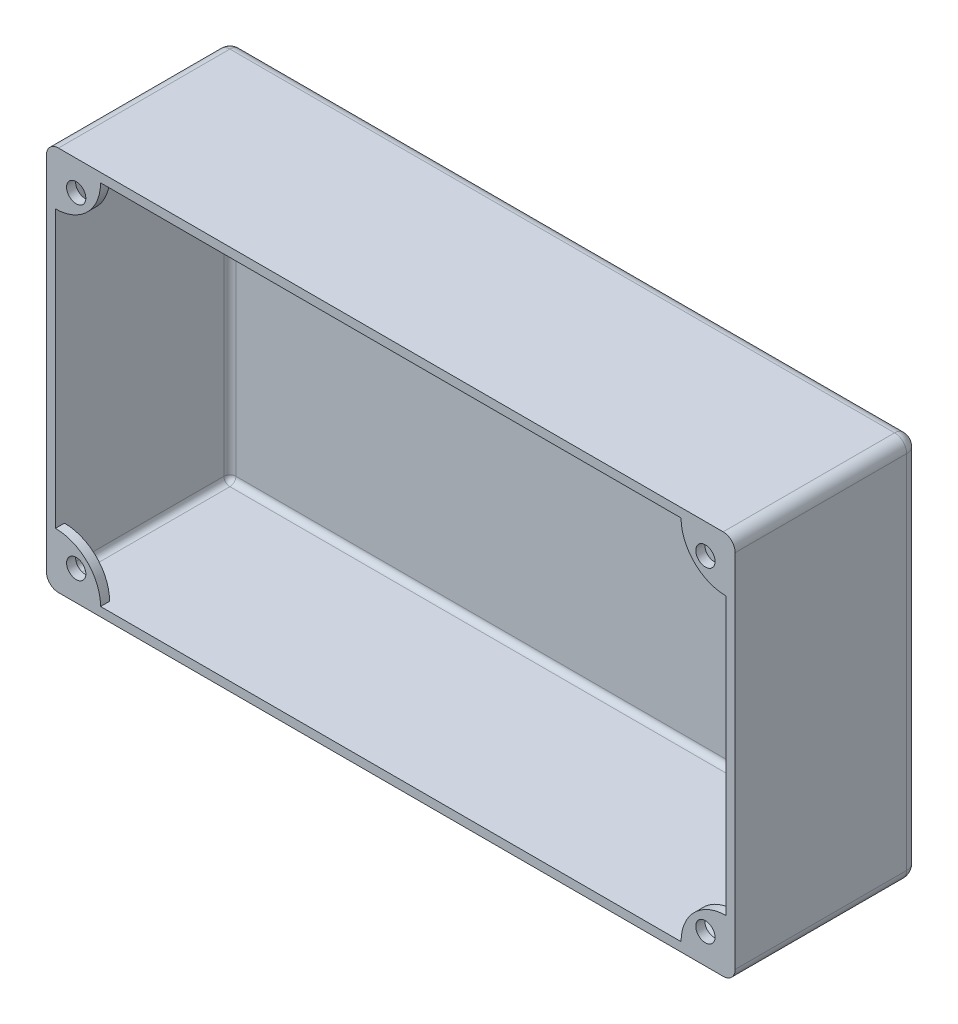
SolidWorks part; units mm, degrees
ref_plane "Plan de face" through (0, 0, 0) normal (0, 0, 1) x (1, 0, 0)
ref_plane "Plan de dessus" through (0, 0, 0) normal (0, 1, 0) x (1, 0, 0)
ref_plane "Plan de droite" through (0, 0, 0) normal (1, 0, 0) x (0, 0, -1)
sketch "Esquisse1" plane through (0, 0, 0) normal (0, 0, 1) x (1, 0, 0)
  line L1 (-78.4653, 42.1965) -> (36.0347, 42.1965)
  line L2 (-78.4653, 42.1965) -> (-78.4653, -21.8035)
  line L3 (-78.4653, -21.8035) -> (36.0347, -21.8035)
  line L4 (36.0347, 42.1965) -> (36.0347, -21.8035)
  line L5 (-78.4653, 42.1965) -> (36.0347, -21.8035) construction
  line L6 (-78.4653, -21.8035) -> (36.0347, 42.1965) construction
  point P0 (-21.2153, 10.1965)
  dimension "D1" = 114.5
  dimension "D2" = 64
extrude "Boss.-Extru.1" add sketch "Esquisse1" along normal blind 30.5
sketch "Esquisse2" plane through (0, 0, 30.5) normal (0, 0, 1) x (1, 0, 0)
  line L0 (-77.9182, 10.1965) -> (36.0347, 10.1965) construction
  line L1 (36.0347, -21.8035) -> (36.0347, 42.1965) construction
  line L2 (36.0347, 42.1965) -> (-78.4653, 42.1965) construction
  line L3 (-78.4653, 42.1965) -> (-78.4653, -21.8035) construction
  line L4 (-21.2153, 42.1965) -> (-21.2153, -21.8035) construction
  line L5 (-78.4653, -21.8035) -> (36.0347, -21.8035) construction
  line L14 (34.5347, -20.3035) -> (34.5347, 40.6965)
  line L15 (34.5347, 40.6965) -> (-76.9653, 40.6965)
  line L16 (-76.9653, 40.6965) -> (-76.9653, -20.3035)
  line L17 (-76.9653, -20.3035) -> (34.5347, -20.3035)
  line L18 (34.5347, -20.3035) -> (34.5347, 40.6965)
  line L19 (34.5347, 40.6965) -> (-76.9653, 40.6965)
  line L20 (-76.9653, 40.6965) -> (-76.9653, -20.3035)
  line L21 (-76.9653, -20.3035) -> (34.5347, -20.3035)
  circle A0 centre (-73.5153, 37.2465) radius 1.6
  circle A1 centre (31.0847, 37.2465) radius 1.6
  circle A2 centre (-73.5153, -16.8535) radius 1.6
  circle A3 centre (31.0847, -16.8535) radius 1.6
  arc A4 (-76.9653, 33.1965) -> (-69.4653, 40.6965) centre (-76.9653, 40.6965) ccw
  arc A5 (-76.9653, -12.8035) -> (-69.4653, -20.3035) centre (-76.9653, -20.3035) cw
  arc A6 (34.5347, -12.8035) -> (27.0347, -20.3035) centre (34.5347, -20.3035) ccw
  arc A7 (34.5347, 33.1965) -> (27.0347, 40.6965) centre (34.5347, 40.6965) cw
  dimension "D1" = 3.2
  dimension "D2" = 4.95
  dimension "D3" = 4.95
  dimension "D5" = 7.5
  dimension "D4" = 1.5
extrude "Enlèv. mat.-Extru.2" cut sketch "Esquisse2" against normal blind 1.5 contours L18 A7 L19 A4 L20 A5 L21 A6 region at (-21.2153, 10.1965, 30.5)
sketch "Esquisse3" plane through (0, 0, 29) normal (0, 0, 1) x (1, 0, 0)
  line L1 (-76.9653, -20.3035) -> (34.5347, -20.3035)
  line L2 (-76.9653, -20.3035) -> (-76.9653, 40.6965)
  line L3 (-76.9653, 40.6965) -> (34.5347, 40.6965)
  line L4 (34.5347, -20.3035) -> (34.5347, 40.6965)
  line L5 (27.0347, 40.6965) -> (-69.4653, 40.6965) construction
  line L6 (-69.4653, -20.3035) -> (27.0347, -20.3035) construction
  line L7 (34.5347, -12.8035) -> (34.5347, 33.1965) construction
  line L8 (-76.9653, 33.1965) -> (-76.9653, -12.8035) construction
  dimension "D1" = 0
  dimension "D2" = 0
  dimension "D3" = 0
  dimension "D4" = 0
extrude "Enlèv. mat.-Extru.3" cut sketch "Esquisse3" against normal blind 27.5
extrude "Enlèv. mat.-Extru.4" cut sketch "Esquisse2<4>" against normal up to next contours A0 | A3 | A2 | A1 region at (-73.5153, 37.2465, 30.5) region at (31.0847, 37.2465, 30.5) region at (-73.5153, -16.8535, 30.5) region at (31.0847, -16.8535, 30.5)
sketch "Esquisse2<4>" plane through (0, 0, 30.5) normal (0, 0, 1) x (1, 0, 0) same geometry as "Esquisse2"
fillet "Congé1" radius 2 8 edges at (-78.4653, 10.1965, 0) (-21.2153, -21.8035, 0) (-21.2153, 42.1965, 0) (36.0347, 10.1965, 0) (-78.4653, -21.8035, 15.25) (-78.4653, 42.1965, 15.25) (36.0347, 42.1965, 15.25) (36.0347, -21.8035, 15.25)
fillet "Congé2" radius 1 8 edges at (-21.2153, 40.6965, 1.5) (34.5347, 10.1965, 1.5) (-21.2153, -20.3035, 1.5) (-76.9653, 10.1965, 1.5) (-76.9653, 40.6965, 15.25) (34.5347, 40.6965, 15.25) (34.5347, -20.3035, 15.25) (-76.9653, -20.3035, 15.25)
